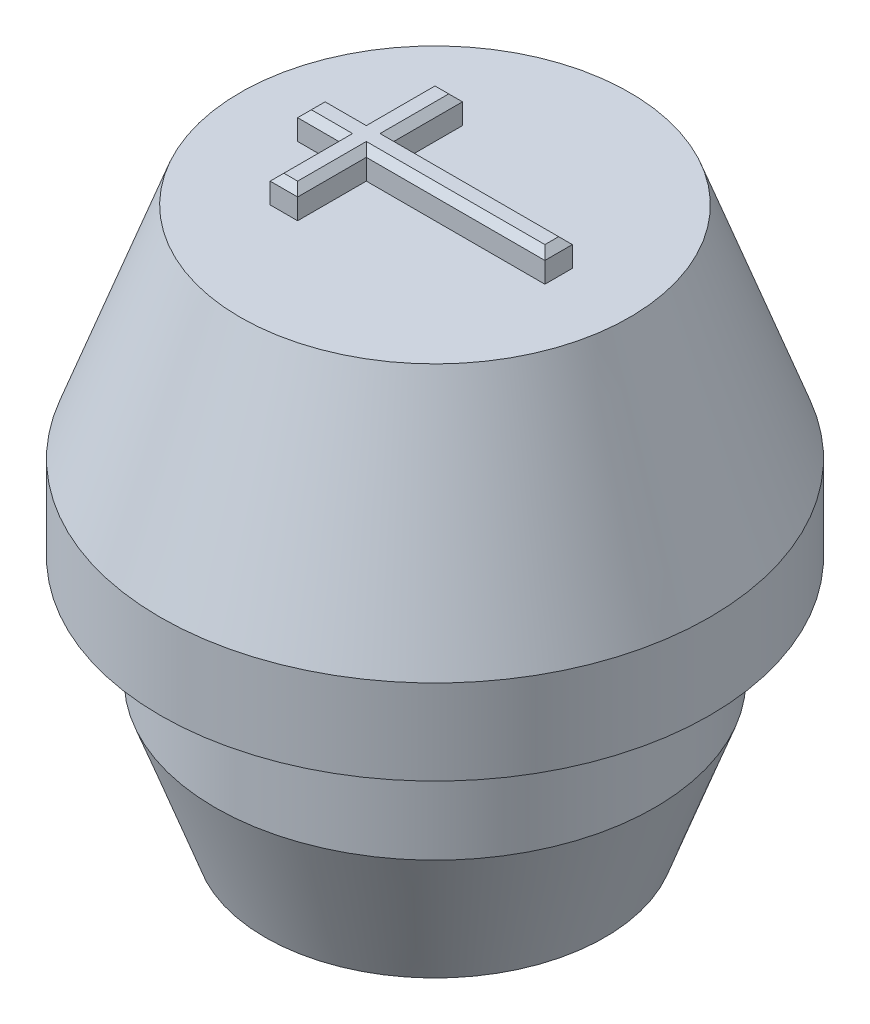
SolidWorks part; units mm, degrees
ref_plane "Front Plane" through (0, 0, 0) normal (0, 0, 1) x (1, 0, 0)
ref_plane "Top Plane" through (0, 0, 0) normal (0, 1, 0) x (1, 0, 0)
ref_plane "Right Plane" through (0, 0, 0) normal (1, 0, 0) x (0, 0, -1)
sketch "Szkic1" plane through (0, 0, 0) normal (0, 1, 0) x (1, 0, 0)
  circle A0 centre (0, 0) radius 8
  point P3 (-4.5993, 0)
extrude "Dodanie-wyciągnięcie2" add sketch "Szkic1" along normal blind 10
sketch "Szkic3" plane through (0, 10, 0) normal (0, 1, 0) x (1, 0, 0)
  circle A0 centre (0, 0) radius 10
extrude "Dodanie-wyciągnięcie3" add sketch "Szkic3" along normal blind 10
sketch "Szkic4" plane through (0, 0, 0) normal (0, -1, 0) x (1, 0, 0)
  circle A0 centre (0, 0) radius 5
extrude "Wytnij-wyciągnięcie1" cut sketch "Szkic4" against normal blind 10
thread "Gwint1" pitch 1.0583 method extrude profile "Profil gwintu1" start angle 0, offset 0, length 10, pitch 1.0583, diameter 10
ref_plane "Płaszczyzna1" through (5, 0, 0) normal (0, 0, 1) x (1, 0, 0)
sketch "Profil gwintu1" plane through (5, 0, 0) normal (0, 0, 1) x (1, 0, 0)
  line L0 (0, 0) -> (0, 1.0583) construction
  line L11 (0, 0) -> (0, 0.926)
  line L12 (0, 0.926) -> (-0.5728, 0.5953)
  line L13 (-0.5728, 0.5953) -> (-0.5728, 0.3307)
  line L15 (-0.5728, 0.3307) -> (0, 0)
  line L17 (-0.5728, 0.463) -> (0, 0.463) construction
  point P2 (0, 0)
  dimension "Pitch" = 1.0583
  dimension "Profile_Angle" = 60
  dimension "Profile_Land" = 0.2646
  dimension "Profile_Height" = 0.5728
chamfer "Sfazowanie1" distance 5 angle 20 2 edges at (0, 0, 8) (0, 10, 8) first distance on face at (0, 10, 8)
chamfer "Sfazowanie2" distance 8 angle 20 1 edges at (0, 20, 10) first distance on face at (0, 8.9081, 10)
sketch "Szkic7" plane through (0, 20, 0) normal (0, 1, 0) x (1, 0, 0)
  line L0 (-4.5, 0) -> (-2.5, 0) construction
  line L1 (4.5, -0.5) -> (-4.5, -0.5)
  line L2 (4.5, -0.5) -> (4.5, 0.5)
  line L3 (4.5, 0.5) -> (-4.5, 0.5)
  line L4 (-4.5, -0.5) -> (-4.5, 0.5)
  line L5 (4.5, -0.5) -> (-4.5, 0.5) construction
  line L6 (4.5, 0.5) -> (-4.5, -0.5) construction
  line L8 (-2, -3) -> (-3, -3)
  line L9 (-2, -3) -> (-2, 3)
  line L10 (-2, 3) -> (-3, 3)
  line L11 (-3, -3) -> (-3, 3)
  line L12 (-2, -3) -> (-3, 3) construction
  line L13 (-2, 3) -> (-3, -3) construction
  point P0 (0, 0)
  dimension "D1" = 1
  dimension "D2" = 9
  dimension "D3" = 6
  dimension "D4" = 1
extrude "Dodanie-wyciągnięcie4" add sketch "Szkic7" along normal blind 1 contours L9 L1 L2 L3 | L11 L8 L9 L1 | L1 L11 L3 L4 | L11 L3 L9 L10 | L11 L1 L9 L3 region at (1.25, 20, 0) region at (-2.5, 20, 1.75) region at (-2.5, 20, 0) region at (-3.75, 20, 0) region at (-2.5, 20, -1.75)
chamfer "Sfazowanie3" distance 0.25 angle 45 12 edges at (4.5, 21, 0) (1.25, 21, 0.5) (-2, 21, 1.75) (-2.5, 21, 3) (-3, 21, 1.75) (-3.75, 21, 0.5) (-4.5, 21, 0) (-3.75, 21, -0.5) (-3, 21, -1.75) (-2.5, 21, -3) (-2, 21, -1.75) (1.25, 21, -0.5)
